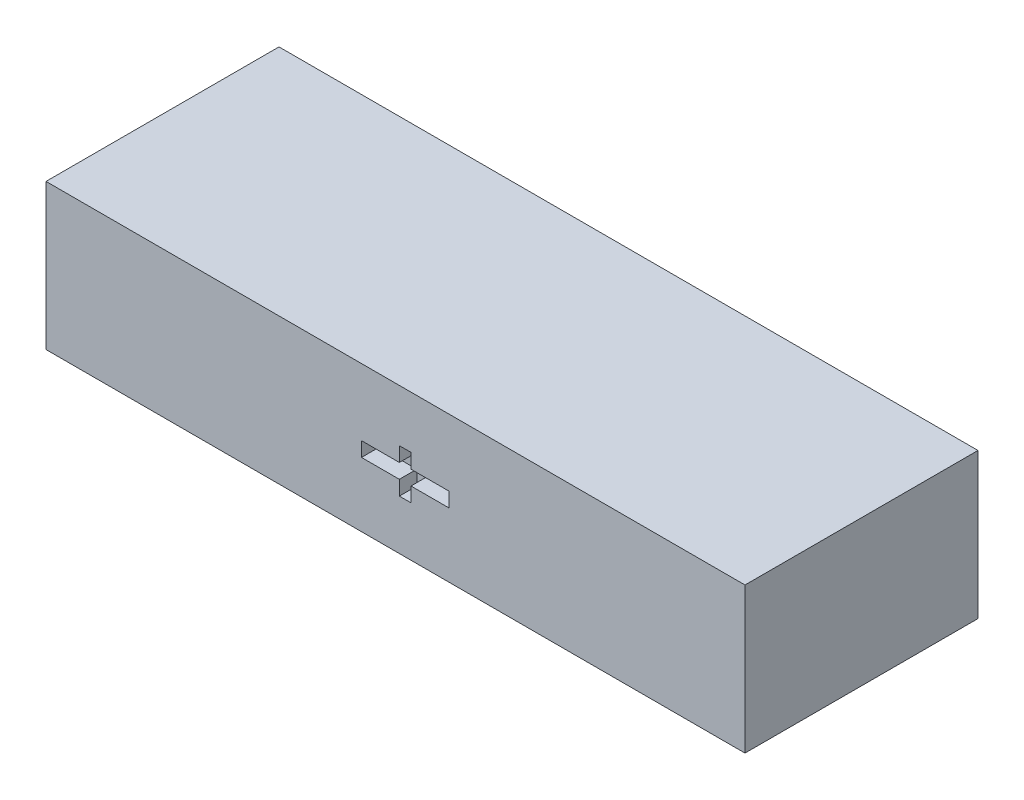
SolidWorks part; units mm, degrees
ref_plane "Front Plane" through (0, 0, 0) normal (0, 0, 1) x (1, 0, 0)
ref_plane "Top Plane" through (0, 0, 0) normal (0, 1, 0) x (1, 0, 0)
ref_plane "Right Plane" through (0, 0, 0) normal (1, 0, 0) x (0, 0, -1)
sketch "Sketch1" plane through (0, 0, 0) normal (0, 1, 0) x (1, 0, 0)
  line L0 (0, 0) -> (0, 80)
  line L1 (0, 80) -> (240, 80)
  line L2 (240, 80) -> (240, 0)
  line L3 (240, 0) -> (0, 0)
  dimension "D1" = 80
  dimension "D2" = 240
extrude "Boss-Extrude1" add sketch "Sketch1" along normal blind 50
sketch "Sketch2" plane through (0, 0, 0) normal (0, 1, 0) x (1, 0, 0)
  line L0 (120, 80) -> (180, 80) construction
  line L1 (240, 80) -> (0, 80) construction
  line L2 (180, 80) -> (180, 0) construction
  line L3 (240, 40) -> (149.3517, 40) construction
  line L5 (200.5, 50.5) -> (200.5, 29.5)
  line L6 (200.5, 50.5) -> (159.5, 50.5)
  line L7 (159.5, 50.5) -> (159.5, 29.5)
  line L8 (200.5, 29.5) -> (159.5, 29.5)
  point P13 (180, 50.5)
  point P14 (200.5, 40)
  point P15 (159.5, 40)
  dimension "D1" = 60
  dimension "D3" = 20.5
extrude "Cut-Extrude1" cut sketch "Sketch2" along normal blind 45
sketch "Sketch3" plane through (0, 0, 0) normal (0, 0, 1) x (1, 0, 0)
  line L0 (37.9188, 24.5841) -> (-38.0812, 24.5841) construction
  line L1 (123.3203, 30.4936) -> (123.3203, -29.5064) construction
  line L2 (123.3203, 24.5841) -> (138.3203, 24.5841) construction
  line L3 (138.3203, 24.5841) -> (138.3203, 27.0841)
  line L4 (138.3203, 24.5841) -> (138.3203, 22.0841)
  line L36 (138.3203, 22.0841) -> (125.3203, 22.0841)
  line L37 (125.3203, 22.0841) -> (125.3203, 17.0841)
  line L38 (125.3203, 17.0841) -> (121.3203, 17.0841)
  line L39 (125.3203, 32.0841) -> (121.3203, 32.0841)
  line L40 (125.3203, 27.0841) -> (125.3203, 32.0841)
  line L41 (138.3203, 27.0841) -> (125.3203, 27.0841)
  line L42 (121.3203, 27.0841) -> (121.3203, 32.0841)
  line L43 (108.3203, 27.0841) -> (121.3203, 27.0841)
  line L44 (108.3203, 24.5841) -> (108.3203, 27.0841)
  line L45 (108.3203, 24.5841) -> (108.3203, 22.0841)
  line L46 (108.3203, 22.0841) -> (121.3203, 22.0841)
  line L47 (121.3203, 22.0841) -> (121.3203, 17.0841)
  point P14 (123.3203, 32.0841)
  point P20 (123.3203, 17.0841)
extrude "Cut-Extrude2" cut sketch "Sketch3" against normal blind 6
